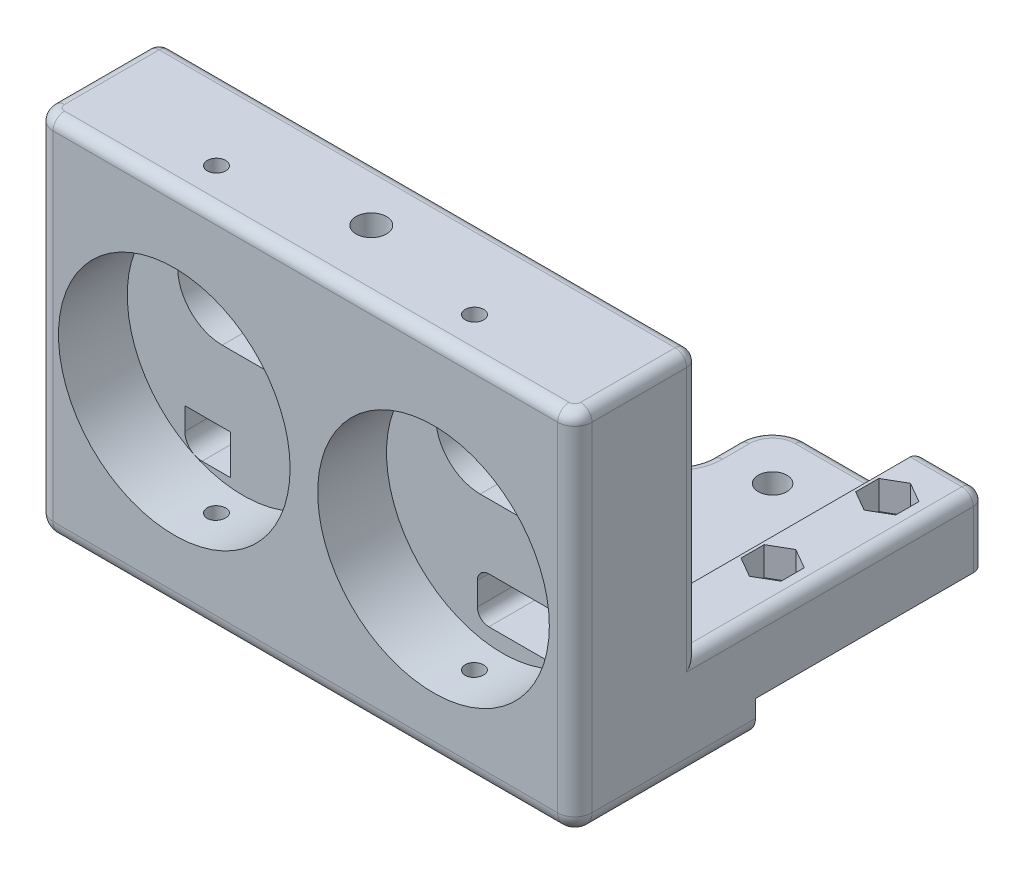
SolidWorks part; units mm, degrees
ref_plane "Ebene vorne" through (0, 0, 0) normal (0, 0, 1) x (1, 0, 0)
ref_plane "Ebene oben" through (0, 0, 0) normal (0, 1, 0) x (1, 0, 0)
ref_plane "Ebene rechts" through (0, 0, 0) normal (1, 0, 0) x (0, 0, -1)
sketch "Skizze1" plane through (0, 0, 0) normal (0, 0, 1) x (1, 0, 0)
  line L1 (174.4691, 28.0437) -> (80.4691, 28.0437)
  line L2 (174.4691, 28.0437) -> (174.4691, -35.9563)
  line L3 (174.4691, -35.9563) -> (80.4691, -35.9563)
  line L4 (80.4691, 28.0437) -> (80.4691, -35.9563)
extrude "Aufsatz-Linear austragen1" add sketch "Skizze1" along normal blind 21.5
sketch "Skizze2" plane through (0, 0, 0) normal (0, 0, -1) x (-1, 0, 0)
  line L5 (-174.4691, -35.9563) -> (-174.4691, 28.0437) construction
  line L6 (-174.4691, -17.9563) -> (-80.4691, -17.9563)
  line L7 (-174.4691, -17.9563) -> (-174.4691, -29.9563)
  line L8 (-174.4691, -29.9563) -> (-80.4691, -29.9563)
  line L9 (-80.4691, -17.9563) -> (-80.4691, -29.9563)
  line L10 (-80.4691, 28.0437) -> (-80.4691, -35.9563) construction
  line L16 (-80.4691, -35.9563) -> (-174.4691, -35.9563) construction
  dimension "D1" = 94
  dimension "D2" = 6
  dimension "D3" = 12
extrude "Aufsatz-Linear austragen2" add sketch "Skizze2" along normal blind 50
fillet "Verrundung1" radius 3 1 edges at (174.4691, -3.9563, 21.5)
sketch "Skizze3" plane through (0, -17.9563, 0) normal (0, 1, 0) x (1, 0, 0)
  line L0 (80.4691, 0) -> (174.4691, 0) construction
  line L1 (111.4691, 0) -> (163.4691, 0)
  line L2 (111.4691, 0) -> (111.4691, 27.1226)
  line L3 (89.4691, 50) -> (163.4691, 50)
  line L4 (163.4691, 0) -> (163.4691, 50)
  line L5 (80.4691, 50) -> (174.4691, 50) construction
  line L6 (80.4691, 50) -> (80.4691, 0) construction
  line L11 (174.4691, 50) -> (174.4691, 0) construction
  line L12 (89.4691, 50) -> (80.4691, 50)
  line L14 (111.4691, 27.1226) -> (102.4691, 27.1226)
  line L15 (80.4691, 50) -> (80.4691, 28.7277)
  line L16 (80.4691, -21.5) -> (80.4691, 0) construction
  line L18 (102.4691, 27.1226) -> (102.4691, 0)
  line L19 (102.4691, 0) -> (80.4691, 0)
  line L20 (80.4691, 28.7277) -> (80.4691, 0)
  dimension "D1" = 31
  dimension "D2" = 50
  dimension "D3" = 11
extrude "Schnitt-Linear austragen1" cut sketch "Skizze3" against normal blind 8
sketch "Skizze6" plane through (0, 0, 0) normal (0, 0, -1) x (-1, 0, 0)
  line L1 (-174.4691, -29.9563) -> (-80.4691, -29.9563)
  line L2 (-174.4691, -29.9563) -> (-174.4691, -35.9563)
  line L3 (-174.4691, -35.9563) -> (-80.4691, -35.9563)
  line L4 (-80.4691, -29.9563) -> (-80.4691, -35.9563)
extrude "Aufsatz-Linear austragen3" add sketch "Skizze6" along direction (0, 0, -1) on the side of the normal blind 10
sketch "Skizze7" plane through (0, 0, 21.5) normal (0, 0, 1) x (1, 0, 0)
  circle A0 centre (104.6099, -4.2584) radius 20.2
  circle A1 centre (149.8248, -5.4669) radius 20.2
extrude "Schnitt-Linear austragen2" cut sketch "Skizze7" against normal blind 12
fillet "Verrundung2" radius 3 1 edges at (80.4691, -3.9563, 21.5)
sketch "Skizze8" plane through (0, 0, 0) normal (0, 0, -1) x (-1, 0, 0)
  line L0 (-111.4691, -25.9563) -> (-163.4691, -25.9563) construction
  line L1 (-102.4473, -15.9563) -> (-94.4473, -15.9563)
  line L2 (-102.4473, -15.9563) -> (-102.4473, -22.8563)
  line L3 (-102.4473, -22.8563) -> (-94.4473, -22.8563)
  line L4 (-94.4473, -15.9563) -> (-94.4473, -22.8563)
  line L5 (-163.4691, -25.9563) -> (-80.4691, -25.9563) construction
  line L6 (-108.9691, 4.1964) -> (-100.9691, 4.1964) construction
  line L7 (-108.9691, 11.9549) -> (-100.9691, 11.9549)
  line L8 (-108.9691, -3.5621) -> (-100.9691, -3.5621)
  line L9 (-153.9691, 4.1964) -> (-145.9691, 4.1964) construction
  line L10 (-153.9691, 11.9549) -> (-145.9691, 11.9549)
  line L11 (-153.9691, -3.5621) -> (-145.9691, -3.5621)
  line L12 (-174.4691, 28.0437) -> (-80.4691, 28.0437) construction
  line L13 (-145.4691, -14.8563) -> (-161.4691, -14.8563)
  line L14 (-145.4691, -14.8563) -> (-145.4691, -22.8563)
  line L15 (-145.4691, -22.8563) -> (-161.4691, -22.8563)
  line L16 (-161.4691, -14.8563) -> (-161.4691, -22.8563)
  line L17 (-174.4691, -17.9563) -> (-174.4691, 28.0437) construction
  arc A0 (-108.9691, 11.9549) -> (-108.9691, -3.5621) centre (-108.9691, 4.1964) ccw
  arc A1 (-100.9691, -3.5621) -> (-100.9691, 11.9549) centre (-100.9691, 4.1964) ccw
  arc A2 (-153.9691, 11.9549) -> (-153.9691, -3.5621) centre (-153.9691, 4.1964) ccw
  arc A3 (-145.9691, -3.5621) -> (-145.9691, 11.9549) centre (-145.9691, 4.1964) ccw
  point P5 (0, 0)
  point P11 (-104.9691, 4.1964)
  point P18 (-149.9691, 4.1964)
  point P29 (-127.4691, 28.0437)
  point P30 (-145.4691, -18.8563)
  dimension "D5" = 22.5
  dimension "D1" = 29
  dimension "D2" = 8
  dimension "D3" = 3.1
  dimension "D4" = 10
  dimension "D6" = 22.5
extrude "Schnitt-Linear austragen3" cut sketch "Skizze8" against normal blind 20
sketch "Skizze9" plane through (0, -29.9563, 0) normal (0, -1, 0) x (-1, 0, 0)
  line L1 (-174.4691, 10) -> (-80.4691, 10) construction
  line L2 (-80.4691, 50) -> (-80.4691, 10) construction
  line L3 (-167.4691, 20) -> (-147.4691, 20) construction
  circle A0 centre (-167.4691, 20) radius 2.5
  circle A1 centre (-147.4691, 20) radius 2.5
  circle A2 centre (-127.4691, 20) radius 2.5
  circle A3 centre (-107.4691, 20) radius 2.5
  circle A4 centre (-87.4691, 20) radius 2.5
  circle A5 centre (-147.4691, 40) radius 2.5
  circle A6 centre (-127.4691, 40) radius 2.5
  circle A7 centre (-107.4691, 40) radius 2.5
  circle A8 centre (-87.4691, 40) radius 2.5
  circle A9 centre (-147.4691, 60) radius 2.5
  circle A10 centre (-127.4691, 60) radius 2.5
  circle A11 centre (-107.4691, 60) radius 2.5
  circle A12 centre (-87.4691, 60) radius 2.5
  circle A13 centre (-167.4691, 40) radius 2.5
  circle A14 centre (-167.4691, 60) radius 2.5
  point P8 (-127.4691, 10)
  dimension "D6" = 5
  dimension "D1" = 10
  dimension "D2" = 87
  dimension "D5" = 20
  dimension "D3" = 5
  dimension "D4" = 3
extrude "Schnitt-Linear austragen4" cut sketch "Skizze9" against normal blind 20
fillet "Verrundung4" radius 3 1 edges at (94.4473, -22.8563, 10)
fillet "Verrundung5" radius 3 5 edges at (80.4691, -35.9563, 4.25) (81.3478, -35.9563, 20.6213) (174.4691, -35.9563, 4.25) (173.5904, -35.9563, 20.6213) (127.4691, -35.9563, 21.5)
sketch "Skizze12" plane through (0, 28.0437, 0) normal (0, 1, 0) x (1, 0, 0)
  circle A0 centre (127.4691, -10) radius 2.65
  circle A1 centre (127.4691, 20) radius 2.5 construction
  dimension "D1" = 0
  dimension "D2" = 30
extrude "Schnitt-Linear austragen6" cut sketch "Skizze12" against normal blind 5.5
sketch "Skizze24" plane through (0, -17.9563, 0) normal (0, 1, 0) x (1, 0, 0)
  line L1 (107.4691, 15.9585) -> (110.9691, 17.9793)
  line L2 (110.9691, 17.9793) -> (110.9691, 22.0207)
  line L3 (110.9691, 22.0207) -> (107.4691, 24.0415)
  line L4 (107.4691, 24.0415) -> (103.9691, 22.0207)
  line L5 (103.9691, 22.0207) -> (103.9691, 17.9793)
  line L6 (103.9691, 17.9793) -> (107.4691, 15.9585)
  circle A0 centre (107.4691, 20) radius 3.5 construction
  dimension "D1" = 7
extrude "Schnitt-Linear austragen12" cut sketch "Skizze24" against normal blind 5
ref_plane "Ebene1" through (102.4473, -15.9563, 0) normal (1, 0, 0) x (0, 0, -1)
sketch "Skizze27" plane through (0, 28.0437, 0) normal (0, 1, 0) x (1, 0, 0)
  line L0 (171.4691, -21.5) -> (83.4691, -21.5) construction
  circle A0 centre (104.9691, -14.5) radius 1.6
  circle A1 centre (149.9691, -14.5) radius 1.6
  circle A2 centre (127.4691, -10) radius 2.65 construction
  dimension "D1" = 22.5
  dimension "D2" = 45
  dimension "D3" = 7
extrude "Schnitt-Linear austragen15" cut sketch "Skizze27" against normal blind 65
fillet "Verrundung9" radius 2 1 edges at (127.4691, 28.0437, 0)
fillet "Verrundung10" radius 2 16 edges at (168.9691, -17.9563, -50) (174.4691, 27.4579, 0.5858) (174.4691, 28.0437, 10.25) (173.5904, 28.0437, 20.6213) (127.4691, 28.0437, 21.5) (81.3478, 28.0437, 20.6213) (80.4691, 28.0437, 10.25) (80.4691, 27.4579, 0.5858) (174.4691, 4.0437, 0) (80.4691, 0.0437, 0) (111.4691, -21.9563, -27.1226) (106.9691, -17.9563, -27.1226) (174.4691, -17.9563, -25) (163.4691, -21.9563, -50) (174.4691, -23.9563, -50) (102.4691, -21.9563, -27.1226)
sketch "Skizze28" plane through (0, 0, 0) normal (0, 0, -1) x (-1, 0, 0)
  line L1 (-127.4691, 26.0437) -> (-127.4691, -29.9563) construction
  line L2 (-82.4691, 26.0437) -> (-172.4691, 26.0437) construction
  line L3 (-80.4691, -29.9563) -> (-174.4691, -29.9563) construction
sketch "Skizze29" plane through (0, 0, 0) normal (0, 0, -1) x (-1, 0, 0)
  circle A0 centre (-100, 17) radius 1.75
extrude "Schnitt-Linear austragen17" cut sketch "Skizze29" against normal blind 4 contours A0
sketch "Skizze30" plane through (0, -29.9563, 0) normal (0, -1, 0) x (1, 0, 0)
  circle A0 centre (97.4691, -30) radius 1.6
  circle A1 centre (87.4691, -20) radius 2.5 construction
  dimension "D1" = 10
  dimension "D2" = 10
extrude "Schnitt-Linear austragen18" cut sketch "Skizze30" against normal blind 8 contours A0
chamfer "Fase3" distance 4 angle 15 1 edges at (97.4691, -29.9563, -31.6) first distance on face at (97.4691, -25.9563, -28.4)
pattern_linear "Lineares Muster2" count 4 spacing 20 along (1, 0, 0) of "Fase3", "Schnitt-Linear austragen18"
sketch "Skizze31" plane through (0, -25.9563, 0) normal (0, 1, 0) x (1, 0, 0)
  line L0 (97.4691, 51.6034) -> (137.3943, 51.6034)
  line L2 (97.4691, 51.6034) -> (97.4691, 33.2724)
  line L3 (97.4691, 33.2724) -> (137.4691, 33.2724)
  line L4 (137.4691, 33.2724) -> (137.3943, 51.6034)
  dimension "40" = 40
extrude "Schnitt-Linear austragen19" cut sketch "Skizze31" against normal blind 4
fillet "Verrundung22" radius 6 4 edges at (137.4691, -27.9563, -33.2724) (137.4008, -27.9563, -50) (97.4691, -27.9563, -50) (97.4691, -27.9563, -33.2724)
fillet "Verrundung23" radius 2 9 edges at (95.7118, -25.9563, -48.2426) (97.4691, -25.9563, -41.6362) (99.2265, -25.9563, -35.0297) (135.6959, -25.9563, -35.0384) (137.435, -25.9563, -41.6362) (139.1741, -25.9563, -48.234) (117.4568, -25.9563, -33.2724) (154.4472, -25.9563, -50) (85.9691, -25.9563, -50)
fillet "Verrundung24" radius 1 10 edges at (163.4691, -25.9563, -24) (111.4691, -25.9563, -12.5613) (80.4691, -28.9563, -50) (80.4691, -25.9563, -23) (80.4691, -26.5421, -49.4142) (164.0549, -26.5421, -49.4142) (106.9691, -25.9563, -27.1226) (110.8833, -25.9563, -26.5369) (102.4691, -25.9563, -12.5613) (103.0549, -25.9563, -26.5369)
fillet "Verrundung26" radius 2 8 edges at (104.9691, 11.9549, 0) (93.2106, 4.1964, 0) (104.9691, -3.5621, 0) (116.7276, 4.1964, 0) (161.7276, 4.1964, 0) (149.9691, 11.9549, 0) (138.2106, 4.1964, 0) (149.9691, -3.5621, 0)
pattern_linear "Lineares Muster3" count 2 spacing 60 along (1, 0, 0) count 2 spacing 20 along (0, 0, -1) of "Schnitt-Linear austragen12"
sketch "Skizze33" plane through (0, -29.9563, 0) normal (0, -1, 0) x (1, 0, 0)
  line L0 (80.4691, -49) -> (80.4691, -10) construction
  line L1 (80.4691, -17.288) -> (102.4691, -17.288)
  line L2 (80.4691, -17.288) -> (80.4691, -25.0338)
  line L3 (80.4691, -25.0338) -> (102.4691, -25.0338)
  line L4 (102.4691, -17.288) -> (102.4691, -25.0338)
  line L6 (80.4691, -43.6328) -> (101.1475, -43.6328)
  line L7 (80.4691, -43.6328) -> (80.4691, -47.9)
  line L8 (80.4691, -47.9) -> (101.1475, -47.9)
  line L9 (101.1475, -43.6328) -> (101.1475, -47.9)
extrude "Schnitt-Linear austragen20" cut sketch "Skizze33" against normal blind 2
sketch "Skizze34" plane through (0, -29.9563, 0) normal (0, -1, 0) x (1, 0, 0)
  line L0 (102.4691, -17.288) -> (80.4691, -17.288) construction
  line L1 (102.4691, -25.0338) -> (100.3126, -25.0338)
  line L2 (102.4691, -25.0338) -> (102.4691, -17.288)
  line L3 (102.4691, -17.288) -> (100.3126, -17.288)
  line L4 (100.3126, -25.0338) -> (100.3126, -17.288)
extrude "Schnitt-Linear austragen22" cut sketch "Skizze34" against normal blind 27
sketch "Skizze35" plane through (0, 0, 9.5) normal (0, 0, 1) x (1, 0, 0)
  circle A0 centre (113.8561, -8) radius 2.3
  circle A1 centre (159.8204, -8) radius 2.3
extrude "Schnitt-Linear austragen23" cut sketch "Skizze35" against normal blind 27
fillet "Verrundung27" radius 2 4 edges at (161.4691, -22.8563, 10) (145.4691, -22.8563, 4.75) (145.4691, -14.8563, 4.75) (161.4691, -14.8563, 4.75)
equation "\"mm\"=0.7"
